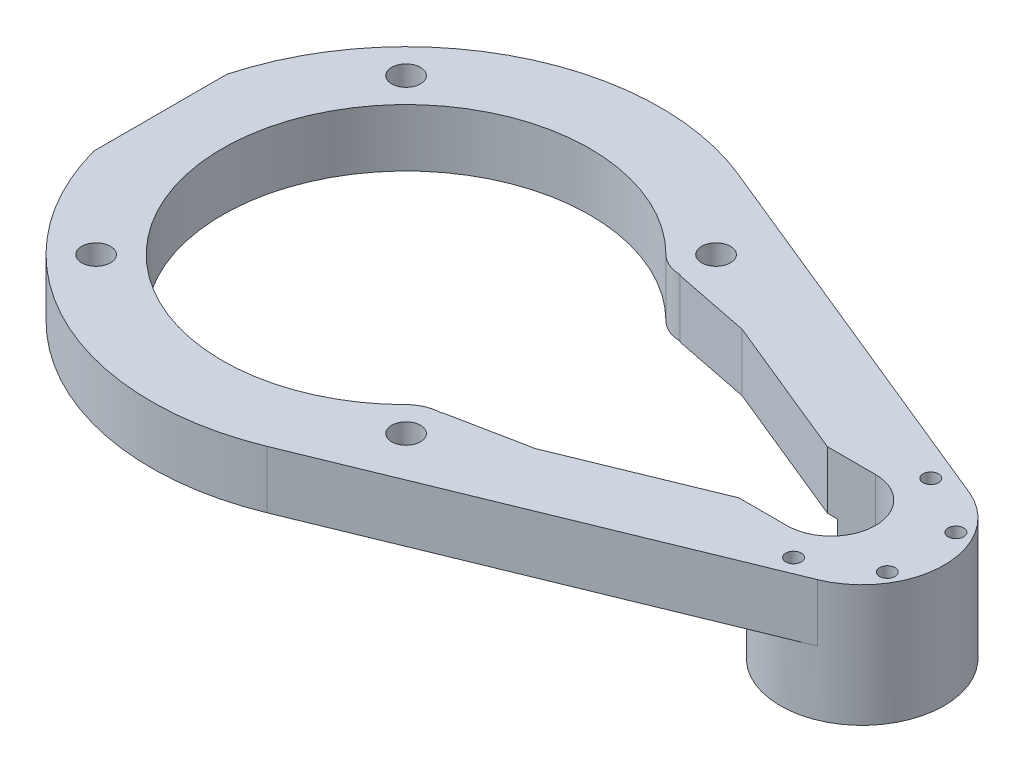
SolidWorks part; units mm, degrees
ref_plane "Front Plane" through (0, 0, 0) normal (0, 0, 1) x (1, 0, 0)
ref_plane "Top Plane" through (0, 0, 0) normal (0, 1, 0) x (1, 0, 0)
ref_plane "Right Plane" through (0, 0, 0) normal (1, 0, 0) x (0, 0, -1)
sketch "Sketch1" plane through (0, 0, 0) normal (0, 1, 0) x (1, 0, 0)
  line L0 (-75.4693, 0) -> (91.4794, 0) construction
  line L1 (35, 35) -> (-35, 35)
  line L2 (35, 35) -> (35, -35)
  line L3 (35, -35) -> (-35, -35)
  line L4 (-35, 35) -> (-35, -35)
  line L5 (35, 35) -> (-35, -35) construction
  line L6 (35, -35) -> (-35, 35) construction
  line L7 (110.0044, 17.1227) -> (21.7695, 53.217)
  line L8 (110.0044, -17.1227) -> (21.7695, -53.217)
  line L9 (86.9809, 9.254) -> (52.5473, 23.3398)
  line L10 (86.9809, -9.254) -> (52.5473, -23.3398)
  line L11 (52.5473, 23.3398) -> (33.4341, 27.1547)
  line L12 (52.5473, -23.3398) -> (33.4341, -27.1547)
  line L13 (-55.5, 15.0236) -> (-55.5, -15.0236)
  line L14 (96, 10) -> (85.1573, 10)
  line L15 (96, -10) -> (85.1573, -10)
  circle A0 centre (-35, 35) radius 3.25
  circle A1 centre (35, 35) radius 3.25
  circle A2 centre (35, -35) radius 3.25
  circle A3 centre (-35, -35) radius 3.25
  circle A4 centre (-35, 35) radius 8
  circle A5 centre (35, 35) radius 8
  circle A6 centre (35, -35) radius 8
  circle A7 centre (-35, -35) radius 8
  circle A8 centre (0, 0) radius 57.4975
  circle A9 centre (0, 0) radius 41.4975
  circle A10 centre (103, 0) radius 18.5
  circle A11 centre (96, 0) radius 10
  point P0 (0, 0)
  dimension "D2" = 6.5
  dimension "D3" = 16
  dimension "D4" = 37
  dimension "D8" = 20
  dimension "D1" = 70
  dimension "D5" = 96
  dimension "D6" = 16
  dimension "D7" = 55.5
  dimension "D9" = 7
extrude "Boss-Extrude1" add sketch "Sketch1" along normal blind 13 contours A9 L1 A5 A8 A4 | L1 A4 L4 A0 | L4 A4 L1 A0 | A9 L1 A4 | A9 L4 A4 A8 A7 | A9 A4 L4 | A9 L4 A7 | A9 A7 L3 | L3 A7 L4 A3 | A9 L3 A7 A8 A6 | L4 A7 L3 A3 | L2 A6 L3 A2 | L3 A6 L2 A2 | A9 L3 A6 | A9 A5 L1 | L1 A5 L2 A1 | L2 A5 L1 A1 | A10 L7 A8 L9 | A10 L10 A8 L8 | A10 | L11 A8 A5 L2 | A6 A8 L12 L2 region at (-31.2062, 0, -31.2062) region at (0, 0, -46.6413) region at (-29.375, 0, -35.2263) region at (-25.7994, 0, -33.5313) region at (-46.2472, 0, 0) region at (-33.5313, 0, -25.7994) region at (25.7994, 0, -33.5313) region at (68.8956, 0, -26.4915) region at (32.0251, 0, -42.182) region at (31.2062, 0, -31.2062) region at (107.2884, 0, 0) region at (45.0485, 0, -28.9885) region at (-33.5313, 0, 25.7994) region at (-42.182, 0, 32.0251) region at (0, 0, 46.6413) region at (-31.2062, 0, 31.2062) region at (-25.7994, 0, 33.5313) region at (68.8956, 0, 26.4915) region at (45.0485, 0, 28.9885) region at (31.2062, 0, 31.2062) region at (25.7994, 0, 33.5313) region at (32.0251, 0, 42.182)
sketch "Sketch2" plane through (0, 0, 0) normal (0, 1, 0) x (1, 0, 0)
  line L0 (96, -10) -> (85.1573, -10) construction
  line L1 (96, 10) -> (85.1573, 10) construction
  line L2 (96, -10) -> (85.1573, -10)
  line L3 (96, 10) -> (85.1573, 10)
  circle A0 centre (103, 0) radius 18.5
  arc A1 (110.0044, -17.1227) -> (110.0044, 17.1227) centre (103, 0) ccw construction
  arc A2 (96, -10) -> (96, 10) centre (96, 0) ccw construction
  arc A3 (96, -10) -> (96, 10) centre (96, 0) ccw
extrude "Boss-Extrude2" add sketch "Sketch2" against normal blind 14.5 contours A0 L3 region at (107.2884, 0, 0)
sketch "Sketch3" plane through (0, -14.5, 0) normal (0, -1, 0) x (1, 0, 0)
  line L0 (103, 18.5) -> (103, -18.5) construction
  line L1 (103, 0) -> (121.5, 0) construction
  line L2 (103, 0) -> (116.4234, 7.75) construction
  line L3 (103, 0) -> (103, 15.5) construction
  arc A0 (87.4356, -10) -> (87.4356, 10) centre (103, 0) ccw construction
  arc A1 (110.0044, 17.1227) -> (87.4356, 10) centre (103, 0) ccw construction
  circle A2 centre (103, 15.5) radius 1.75
  circle A3 centre (116.4234, 7.75) radius 1.75
  circle A4 centre (116.4234, -7.75) radius 1.75
  circle A5 centre (103, -15.5) radius 1.75
  circle A6 centre (89.5766, -7.75) radius 1.75 [skipped]
  circle A7 centre (89.5766, 7.75) radius 1.75 [skipped]
  point P11 (103, 0)
  point P27 (103, 0)
  dimension "D1" = 3.5
  dimension "D2" = 15.5
  dimension "D3" = 6
extrude "Cut-Extrude1" cut sketch "Sketch3" against normal up to next
sketch "Sketch4" plane through (0, 0, 0) normal (0, -1, 0) x (1, 0, 0)
  line L0 (-38.7123, 38.7123) -> (-35, 35) construction
  line L1 (-29.1444, 33.431) -> (-30.7134, 39.2866)
  line L2 (-30.7134, 39.2866) -> (-36.569, 40.8556)
  line L3 (-36.569, 40.8556) -> (-40.8556, 36.569)
  line L4 (-40.8556, 36.569) -> (-39.2866, 30.7134)
  line L5 (-39.2866, 30.7134) -> (-33.431, 29.1444)
  line L6 (-33.431, 29.1444) -> (-29.1444, 33.431)
  line L7 (36.569, 40.8556) -> (30.7134, 39.2866)
  line L8 (40.8556, 36.569) -> (36.569, 40.8556)
  line L9 (39.2866, 30.7134) -> (40.8556, 36.569)
  line L10 (33.431, 29.1444) -> (39.2866, 30.7134)
  line L11 (29.1444, 33.431) -> (33.431, 29.1444)
  line L12 (30.7134, 39.2866) -> (29.1444, 33.431)
  line L13 (40.8556, -36.569) -> (39.2866, -30.7134)
  line L14 (36.569, -40.8556) -> (40.8556, -36.569)
  line L15 (30.7134, -39.2866) -> (36.569, -40.8556)
  line L16 (29.1444, -33.431) -> (30.7134, -39.2866)
  line L17 (33.431, -29.1444) -> (29.1444, -33.431)
  line L18 (39.2866, -30.7134) -> (33.431, -29.1444)
  line L19 (-36.569, -40.8556) -> (-30.7134, -39.2866)
  line L20 (-40.8556, -36.569) -> (-36.569, -40.8556)
  line L21 (-39.2866, -30.7134) -> (-40.8556, -36.569)
  line L22 (-33.431, -29.1444) -> (-39.2866, -30.7134)
  line L23 (-29.1444, -33.431) -> (-33.431, -29.1444)
  line L24 (-30.7134, -39.2866) -> (-29.1444, -33.431)
  line L25 (0, 13.683) -> (0, -11.8209) construction
  circle A0 centre (0, 0) radius 49.4975
  circle A1 centre (-35, 35) radius 5.25 construction
  point P15 (0, 0)
  point P34 (0, 0)
  circle M27 centre (35, 35) radius 3.25
  circle M28 centre (-35, 35) radius 3.25
  circle M47 centre (-35, -35) radius 3.25
  circle M48 centre (35, -35) radius 3.25
  dimension "D1" = 10.5
  dimension "D2" = 4
extrude "Cut-Extrude2" cut sketch "Sketch4" against normal blind 1.2 contours L1 A0 L5 L6 M28 | A0 L1 L2 L3 L4 L5 M28 | L10 A0 L12 L11 M27 | A0 L10 L9 L8 L7 L12 M27 | L16 A0 L18 L17 M48 | A0 L16 L15 L14 L13 L18 M48 | A0 L22 L21 L20 L19 L24 M47 | L22 A0 L24 L23 M47 region at (-31.3852, 0, 31.3852) region at (-31.7222, 0, 38.1846) region at (31.5415, 0, 37.9671) region at (30.8013, 0, 39.0549) region at (-38.1846, 0, -31.7222) region at (-36.1289, 0, -30.0101) region at (37.9671, 0, -31.5415) region at (39.0549, 0, -30.8013)
